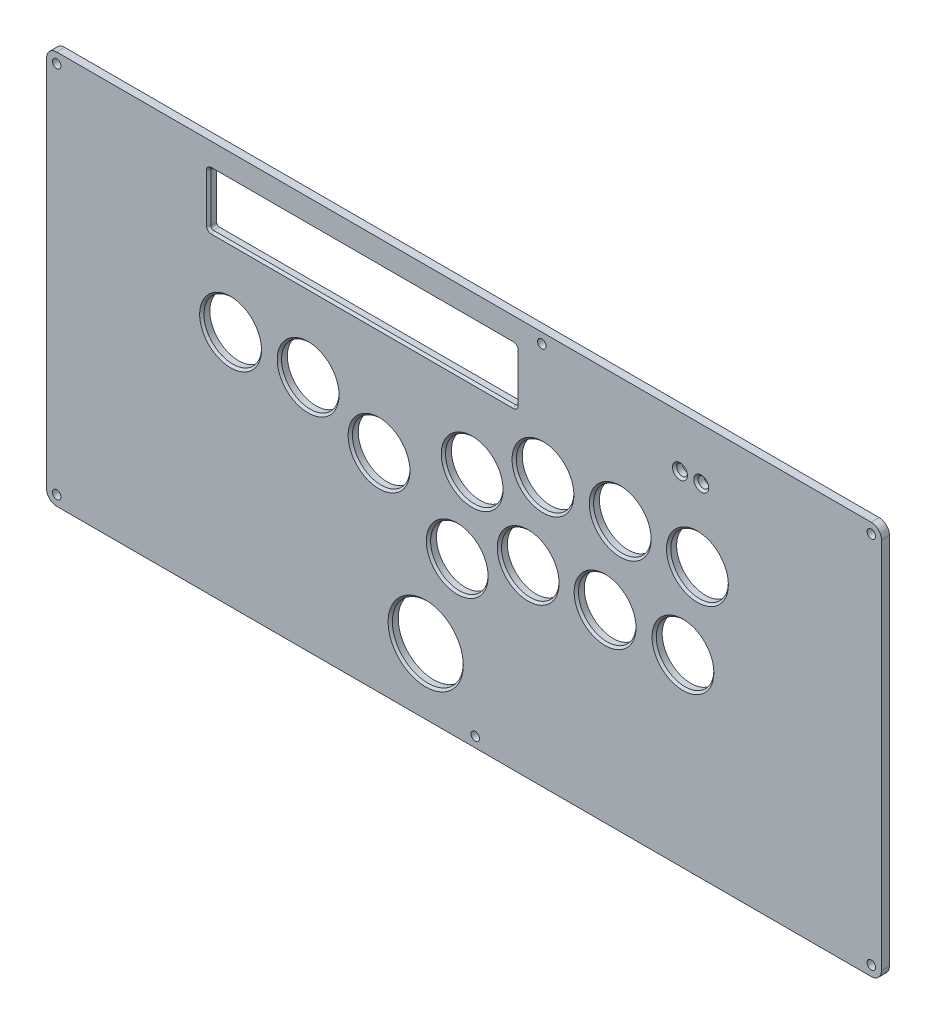
SolidWorks part; units mm, degrees
material "ABS PC"
ref_plane "Front Plane" through (0, 0, 0) normal (0, 0, 1) x (1, 0, 0)
ref_plane "Top Plane" through (0, 0, 0) normal (0, 1, 0) x (1, 0, 0)
ref_plane "Right Plane" through (0, 0, 0) normal (1, 0, 0) x (0, 0, -1)
sketch "草图1" plane through (0, 0, 0) normal (0, 0, 1) x (1, 0, 0)
  line L0 (463.05, 491.925) -> (463.05, 473.875)
  line L1 (464.05, 472.875) -> (577.35, 472.875)
  line L2 (578.35, 473.875) -> (578.35, 491.925)
  line L3 (711.6255, 502.225) -> (406.05, 502.225)
  line L4 (402.25, 358.425) -> (402.25, 498.425)
  line L5 (711.6255, 354.625) -> (406.05, 354.625)
  line L6 (715.4255, 498.425) -> (715.4255, 358.425)
  line L7 (588.05, 502.225) -> (406.05, 502.225)
  line L8 (464.05, 492.925) -> (577.35, 492.925)
  circle A0 centre (544.4688, 379.2689) radius 13.3
  circle A1 centre (471.2738, 443.8389) radius 10.8
  circle A2 centre (500.3688, 443.7189) radius 10.8
  circle A3 centre (526.9688, 432.3689) radius 10.8
  circle A4 centre (561.9088, 443.7789) radius 10.8
  circle A5 centre (582.9088, 423.8489) radius 10.8
  circle A6 centre (556.2988, 412.7389) radius 10.8
  circle A7 centre (588.4688, 455.3089) radius 10.8
  circle A8 centre (611.7588, 423.8489) radius 10.8
  circle A9 centre (617.4388, 455.4289) radius 10.8
  circle A10 centre (646.4088, 455.1889) radius 10.8
  circle A11 centre (640.9688, 423.8489) radius 10.8
  arc A12 (715.4255, 498.425) -> (711.6255, 502.225) centre (711.6255, 498.425) ccw
  arc A13 (711.6255, 354.625) -> (715.4255, 358.425) centre (711.6255, 358.425) ccw
  arc A14 (402.25, 358.425) -> (406.05, 354.625) centre (406.05, 358.425) ccw
  arc A15 (406.05, 502.225) -> (402.25, 498.425) centre (406.05, 498.425) ccw
  circle A16 centre (563.05, 358.425) radius 3.25
  circle A17 centre (711.6255, 498.425) radius 3.25
  circle A18 centre (406.05, 498.425) radius 3.25
  circle A19 centre (406.05, 358.425) radius 3.25
  circle A20 centre (711.6255, 358.425) radius 3.25
  circle A21 centre (588.05, 498.425) radius 3.25
  circle A22 centre (639.8539, 482.9) radius 2
  circle A23 centre (647.8539, 482.9) radius 2
  circle A24 centre (711.6255, 358.425) radius 1.6
  circle A25 centre (711.6255, 498.425) radius 1.6
  circle A26 centre (563.05, 358.425) radius 1.6
  circle A27 centre (588.05, 498.425) radius 1.6
  circle A28 centre (406.05, 498.425) radius 1.6
  circle A29 centre (406.05, 358.425) radius 1.6
  arc A30 (464.05, 492.925) -> (463.05, 491.925) centre (464.05, 491.925) ccw
  arc A31 (463.05, 473.875) -> (464.05, 472.875) centre (464.05, 473.875) ccw
  arc A32 (578.35, 491.925) -> (577.35, 492.925) centre (577.35, 491.925) ccw
  arc A33 (577.35, 472.875) -> (578.35, 473.875) centre (577.35, 473.875) ccw
extrude "凸台-拉伸1" add sketch "草图1" against normal blind 3 contours A15 L4 A14 L5 A13 L6 A12 L3
extrude "切除-拉伸1" cut sketch "草图1<3>" against normal through all from surface contours L8 A32 L2 A33 L1 A31 L0 A30 starting at face at (558.8378, 428.425, 0)
sketch "草图1<3>" plane through (0, 0, 0) normal (0, 0, 1) x (1, 0, 0) same geometry as "草图1"
extrude "切除-拉伸2" cut sketch "草图1<4>" against normal through all from surface contours A1 | A2 | A3 | A0 | A6 | A4 | A5 | A7 | A8 | A9 | A11 | A10 | A22 | A23 starting at face at (520.7, 482.9, 0)
sketch "草图1<4>" plane through (0, 0, 0) normal (0, 0, 1) x (1, 0, 0) same geometry as "草图1"
extrude "切除-拉伸3" cut sketch "草图1<5>" against normal through all from surface contours A24 | A25 | A26 | A27 | A29 | A28 starting at face at (482.0738, 443.8389, 0)
sketch "草图1<5>" plane through (0, 0, 0) normal (0, 0, 1) x (1, 0, 0) same geometry as "草图1"
chamfer "倒角2" distance 0.8 36 edges at (714.3125, 501.112, 0) (715.4255, 428.425, 0) (714.3125, 355.738, 0) (558.8378, 354.625, 0) (403.363, 355.738, 0) (402.25, 428.425, 0) (403.363, 501.112, 0) (558.8378, 502.225, 0) (520.7, 492.925, 0) (463.3429, 492.6321, 0) (463.05, 482.9, 0) (463.3429, 473.1679, 0) (520.7, 472.875, 0) (578.0571, 473.1679, 0) (578.35, 482.9, 0) (578.0571, 492.6321, 0) (593.7088, 423.8489, 0) (572.7088, 443.7789, 0) (599.2688, 455.3089, 0) (622.5588, 423.8489, 0) (511.1688, 443.7189, 0) (537.7688, 432.3689, 0) (557.7688, 379.2689, 0) (567.0988, 412.7389, 0) (649.8539, 482.9, 0) (628.2388, 455.4289, 0) (651.7688, 423.8489, 0) (657.2088, 455.1889, 0) (641.8539, 482.9, 0) (482.0738, 443.8389, 0) (713.2255, 358.425, 0) (407.65, 498.425, 0) (713.2255, 498.425, 0) (564.65, 358.425, 0) (589.65, 498.425, 0) (407.65, 358.425, 0)
other "删除面2" face at (558.8378, 501.825, -0.4) face at (403.9979, 500.4771, -0.4) face at (402.65, 428.425, -0.4) face at (403.9979, 356.3729, -0.4) face at (558.8378, 355.025, -0.4) face at (713.6776, 500.4771, -0.4) face at (715.0255, 428.425, -0.4) face at (713.6776, 356.3729, -0.4) and patch yes
other "删除面3" face at (714.0255, 358.425, 0) and patch yes
other "删除面4" face at (408.45, 498.425, 0) and patch yes
other "删除面5" face at (565.45, 358.425, 0) and patch yes
other "删除面6" face at (714.0255, 498.425, 0) and patch yes
other "删除面7" face at (590.45, 498.425, 0) and patch yes
other "删除面8" face at (408.45, 358.425, 0) and patch yes
